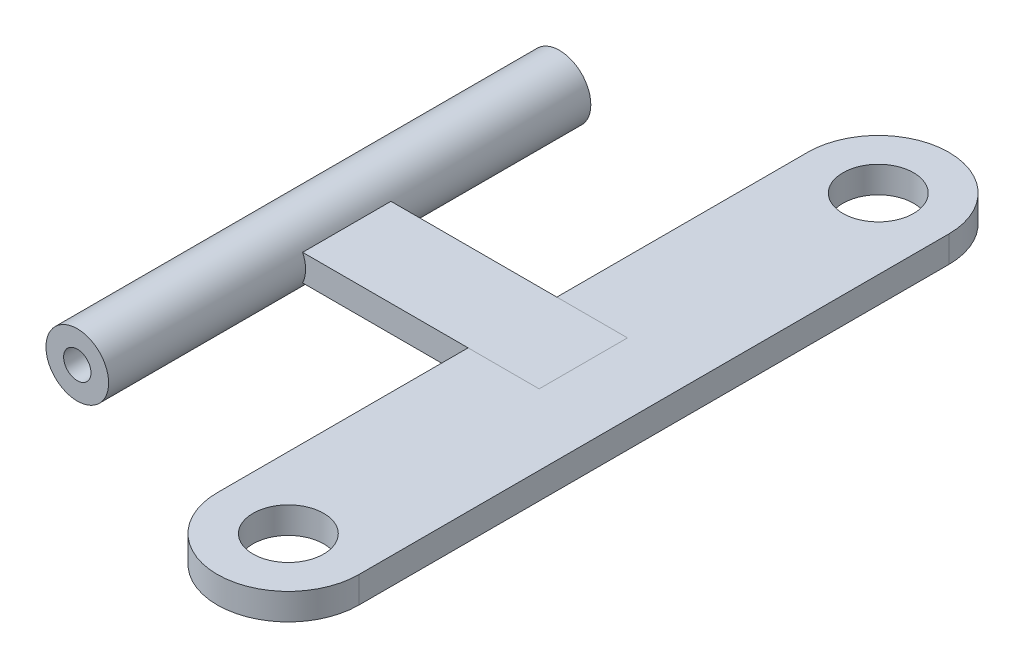
SolidWorks part; units mm, degrees
ref_plane "Front Plane" through (0, 0, 0) normal (0, 0, 1) x (1, 0, 0)
ref_plane "Top Plane" through (0, 0, 0) normal (0, 1, 0) x (1, 0, 0)
ref_plane "Right Plane" through (0, 0, 0) normal (1, 0, 0) x (0, 0, -1)
sketch "Sketch1" plane through (0, 0, 0) normal (0, 0, 1) x (1, 0, 0)
  circle A0 centre (0, 0) radius 1.9685
  circle A1 centre (0, 0) radius 4.5085
  dimension "D1" = 3.937
  dimension "D2" = 2.54
extrude "Boss-Extrude1" add sketch "Sketch1" along normal blind 34.671 and the other way blind 34.671
sketch "Sketch3" plane through (0, 0, 0) normal (0, 0, 1) x (1, 0, 0)
  line L0 (0, 0) -> (1.9685, 0) construction
  line L1 (1.9685, 1.905) -> (1.9685, -1.905)
  line L3 (1.9685, -1.905) -> (38.1, -1.905)
  line L4 (1.9685, -1.905) -> (1.9685, 1.905)
  line L5 (1.9685, 1.905) -> (38.1, 1.905)
  line L6 (38.1, -1.905) -> (38.1, 1.905)
  circle A0 centre (0, 0) radius 1.9685 construction
  point P9 (1.9685, 0)
  dimension "D1" = 3.81
  dimension "D2" = 38.1
extrude "Boss-Extrude2" add sketch "Sketch3" along normal blind 6.35 and the other way blind 6.35 contours L3 L6 L5 L1 L4 region at (20.0343, 0, 0)
sketch "Sketch5" plane through (0, 1.905, 0) normal (0, 1, 0) x (1, 0, 0)
  line L0 (0, 0) -> (38.1, 0) construction
  line L1 (38.1, 6.35) -> (38.1, -6.35) construction
  line L2 (38.1, -42.418) -> (38.1, 42.418) construction
  line L3 (27.8805, -42.418) -> (27.8805, -6.35)
  line L4 (4.0863, -6.35) -> (38.1, -6.35) construction
  line L5 (48.26, 42.418) -> (27.94, 42.418) construction
  line L6 (4.0863, 6.35) -> (38.1, 6.35) construction
  line L7 (27.94, 6.35) -> (27.94, 42.418)
  line L8 (48.26, 42.418) -> (48.26, -42.418)
  line L9 (27.94, 6.35) -> (38.1, 6.35)
  line L10 (38.1, 6.35) -> (38.1, -6.35)
  line L11 (38.1, -6.35) -> (27.8805, -6.35)
  circle A0 centre (38.1, -42.418) radius 5.08
  circle A1 centre (38.1, 42.418) radius 5.08
  arc A2 (27.94, 42.418) -> (48.26, 42.418) centre (38.1, 42.418) cw
  arc A3 (27.8805, -42.418) -> (48.26, -42.418) centre (38.0703, -42.418) ccw
  point P8 (38.1, 0)
  point P21 (38.1, 42.418)
  dimension "D2" = 10.16
  dimension "D3" = 10.16
  dimension "D1" = 84.836
  dimension "D4" = 20.32
extrude "Boss-Extrude3" add sketch "Sketch5" against normal up to vertex (3.81 mm away) separate body up to point (4.0863, -1.905, -6.35)
